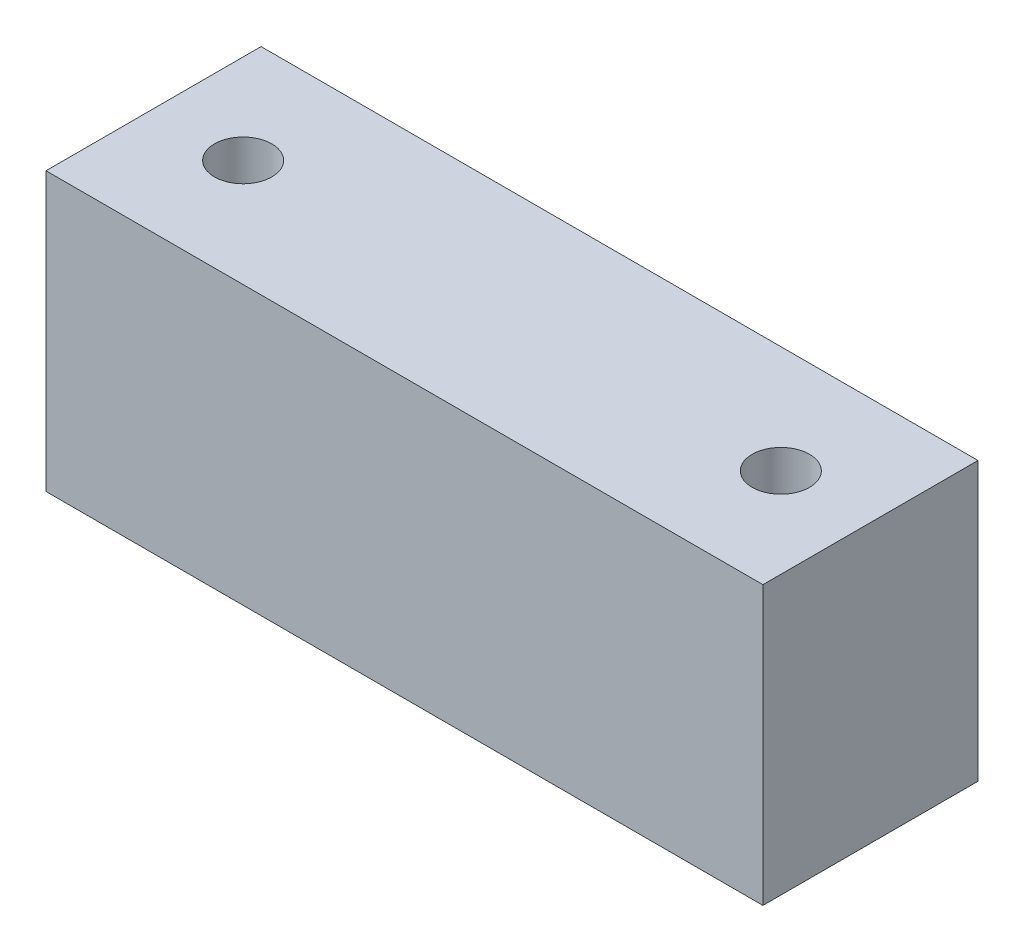
SolidWorks part; units mm, degrees
ref_plane "Front Plane" through (0, 0, 0) normal (0, 0, 1) x (1, 0, 0)
ref_plane "Top Plane" through (0, 0, 0) normal (0, 1, 0) x (1, 0, 0)
ref_plane "Right Plane" through (0, 0, 0) normal (1, 0, 0) x (0, 0, -1)
sketch "Sketch1" plane through (0, 0, 0) normal (0, 1, 0) x (1, 0, 0)
  line L1 (-20, 6) -> (20, 6)
  line L2 (-20, 6) -> (-20, -6)
  line L3 (-20, -6) -> (20, -6)
  line L4 (20, 6) -> (20, -6)
  line L5 (-20, 6) -> (20, -6) construction
  line L6 (-20, -6) -> (20, 6) construction
  point P0 (0, 0)
  dimension "D1" = 40
  dimension "D2" = 12
extrude "Boss-Extrude1" add sketch "Sketch1" along normal blind 15.5
sketch "Sketch2" plane through (0, 15.5, 0) normal (0, 1, 0) x (1, 0, 0)
  line L0 (-20, 0) -> (20, 0) construction
  line L1 (-20, 6) -> (-20, -6) construction
  line L2 (20, -6) -> (20, 6) construction
  line L3 (0, -6) -> (0, 7.5) construction
  line L4 (-20, -6) -> (20, -6) construction
  line L5 (20, 6) -> (-20, 6) construction
  circle A0 centre (15, 0) radius 1.6
  circle A1 centre (-15, 0) radius 1.6
  point P17 (0, 6)
  dimension "D1" = 3.2
  dimension "D2" = 15
extrude "Cut-Extrude2" cut sketch "Sketch2" against normal through all
sketch "Sketch3" plane through (-20, 0, 0) normal (-1, 0, 0) x (0, 0, 1)
  line L0 (-5.25, 15.5) -> (-5.25, 14.5)
  line L1 (-6, 15.5) -> (6, 15.5) construction
  line L2 (-5.25, 14.5) -> (-4.25, 14.5)
  line L3 (-4.25, 14.5) -> (-4.25, 15.5)
  line L4 (-4.25, 15.5) -> (-5.25, 15.5)
  line L5 (-3.25, 14.5) -> (-2.25, 14.5)
  line L6 (-3.25, 15.5) -> (-3.25, 14.5)
  line L7 (-2.25, 14.5) -> (-2.25, 15.5)
  line L8 (-2.25, 15.5) -> (-3.25, 15.5)
  line L9 (-1.25, 14.5) -> (-0.25, 14.5)
  line L10 (-1.25, 15.5) -> (-1.25, 14.5)
  line L11 (-0.25, 14.5) -> (-0.25, 15.5)
  line L12 (-0.25, 15.5) -> (-1.25, 15.5)
  line L13 (0.75, 14.5) -> (1.75, 14.5)
  line L14 (0.75, 15.5) -> (0.75, 14.5)
  line L15 (1.75, 14.5) -> (1.75, 15.5)
  line L16 (1.75, 15.5) -> (0.75, 15.5)
  line L17 (2.75, 14.5) -> (3.75, 14.5)
  line L18 (2.75, 15.5) -> (2.75, 14.5)
  line L19 (3.75, 14.5) -> (3.75, 15.5)
  line L20 (3.75, 15.5) -> (2.75, 15.5)
  line L21 (4.75, 14.5) -> (5.75, 14.5)
  line L22 (4.75, 15.5) -> (4.75, 14.5)
  line L23 (5.75, 14.5) -> (5.75, 15.5)
  line L24 (5.75, 15.5) -> (4.75, 15.5)
  line L25 (6.75, 14.5) -> (7.75, 14.5)
  line L26 (6.75, 15.5) -> (6.75, 14.5)
  line L27 (7.75, 14.5) -> (7.75, 15.5)
  line L28 (7.75, 15.5) -> (6.75, 15.5)
  line L29 (8.75, 14.5) -> (9.75, 14.5)
  line L30 (8.75, 15.5) -> (8.75, 14.5)
  line L31 (9.75, 14.5) -> (9.75, 15.5)
  line L32 (9.75, 15.5) -> (8.75, 15.5)
  line L33 (-6, 15.5) -> (-6, 0) construction
  dimension "D1" = 1
  dimension "D3" = 0.75
  dimension "D4" = 1
  dimension "D5" = 1
  dimension "D6" = 1
  dimension "D2" = 8
extrude "Teeth" [suppressed] cut sketch "Sketch3" against normal blind 5 and the other way blind 5 from surface starting at plane "Right Plane"
sketch "Sketch4" [suppressed] plane through (0, 5, 0) normal (0, 1, 0) x (1, 0, 0)
  line L0 (-15, 0) -> (-15, 3.4641) construction
  line L1 (-15, 3.4641) -> (-18, 1.7321)
  line L2 (-18, 1.7321) -> (-18, -1.7321)
  line L3 (-18, -1.7321) -> (-15, -3.4641)
  line L4 (-15, -3.4641) -> (-12, -1.7321)
  line L5 (-12, -1.7321) -> (-12, 1.7321)
  line L6 (-12, 1.7321) -> (-15, 3.4641)
  line L7 (0, 7.5) -> (0, -7.5) construction
  line L8 (20, 7.5) -> (-20, 7.5) construction
  line L9 (5, -7.5) -> (-5, -7.5) construction
  line L10 (15, 0) -> (15, 3.4641) construction
  line L11 (12, 1.7321) -> (15, 3.4641)
  line L12 (12, -1.7321) -> (12, 1.7321)
  line L13 (15, -3.4641) -> (12, -1.7321)
  line L14 (18, -1.7321) -> (15, -3.4641)
  line L15 (18, 1.7321) -> (18, -1.7321)
  line L16 (15, 3.4641) -> (18, 1.7321)
  line L17 (-15, 0) -> (-15, 3.4641) construction
  circle A0 centre (-15, 0) radius 3 construction
  circle A1 centre (15, 0) radius 3 construction
  dimension "D1" = 6
extrude "Cut-Extrude4" [suppressed] cut sketch "Sketch4" against normal blind 2
equation "\"X-ROD-SPACING\"=45"
equation "\"Y-ROD-SPACING\"=75"
equation "\"Z-ROD-SPACING\"=17.5"
equation "\"Y-BED-OFFSET\"=2"
equation "\"Y-BED-ROD-INSET\"=3.5"
equation "\"T-SLOT-NUT-FILLET-RADIUS\"=0.25"
equation "\"T-SLOT-SCREW-SHAFT-RADIUS\"=1.75"
equation "\"T-SLOT-SCREW-SHAFT-CUTOUT-LENGTH\"=10.5"
equation "\"T-SLOT-NUT-DEPTH\"=4.2"
equation "\"T-SLOT-NUT-WIDTH\"=3"
equation "\"T-SLOT-NUT-END-DISTANCE\"=8"
equation "\"ACRYLIC-THICKNESS\"=10"
equation "\"ACRYLIC-THICKNESS2\"=4.5"
equation "\"ACRYLIC-TAB-CUTOUT-SIZE\"=\"ACRYLIC-THICKNESS\"+\"ACRYLIC-TAB-TOLERANCE\"*2"
equation "\"ACRYLIC-TAB-WIDTH\"=\"ACRYLIC-THICKNESS\""
equation "\"ACRYLIC-M3-HOLE\"=3.1"
equation "\"SMOOTHROD-CAP-SCREW-DISTANCE\"=20"
equation "\"FRAME-WIDTH-INNER\"=370"
equation "\"NEMA17-HOLE-SPACING\"=31"
equation "\"NEMA17-CENTRAL-CUTOUT\"=22.5"
equation "\"Z-BRACKET-REACH\"=55"
equation "\"TOP-BRACKET-SPACING\"=40"
equation "\"SMOOTHROD-X-LENGTH\"=350"
equation "\"SMOOTHROD-Y-LENGTH\"=350"
equation "\"SMOOTHROD-Z-LENGTH\"=350"
equation "\"SMOOTHROD-TIGHTENING-HEADROOM\"=.25"
equation "\"LEADSCREW-Z-LENGTH\"=300"
equation "\"SCREW-LENGTH-FRAME\"=\"ACRYLIC-THICKNESS\" + 10"
equation "\"SCREW-HEAD-RADIUS\"=6"
equation "\"PRINTED-X-SMOOTHROD-DIAMETER\"=8.2"
equation "\"PRINTED-X-SMOOTHROD-CUTOUT\"=10"
equation "\"PRINTED-X-BASE-HEIGHT\"=10"
equation "\"PRINTED-LM8UU-CUTOUT-SIZE\"=15.25"
equation "\"PRINTED-LM8UU-CUTOUT-LENGTH\"=24.5"
equation "\"PRINTED-X-IDLER-HEIGHT\"=16"
equation "\"PSU-MOUNTING-WIDTH\"=95"
equation "\"PSU-MOUNTING-HEIGHT\"=177"
equation "\"Y-BELT-TO-ROD-DISTANCE\"=20"
equation "\"D1@Sketch4\"=\"T-SLOT-NUT-WIDTH\"*2"
